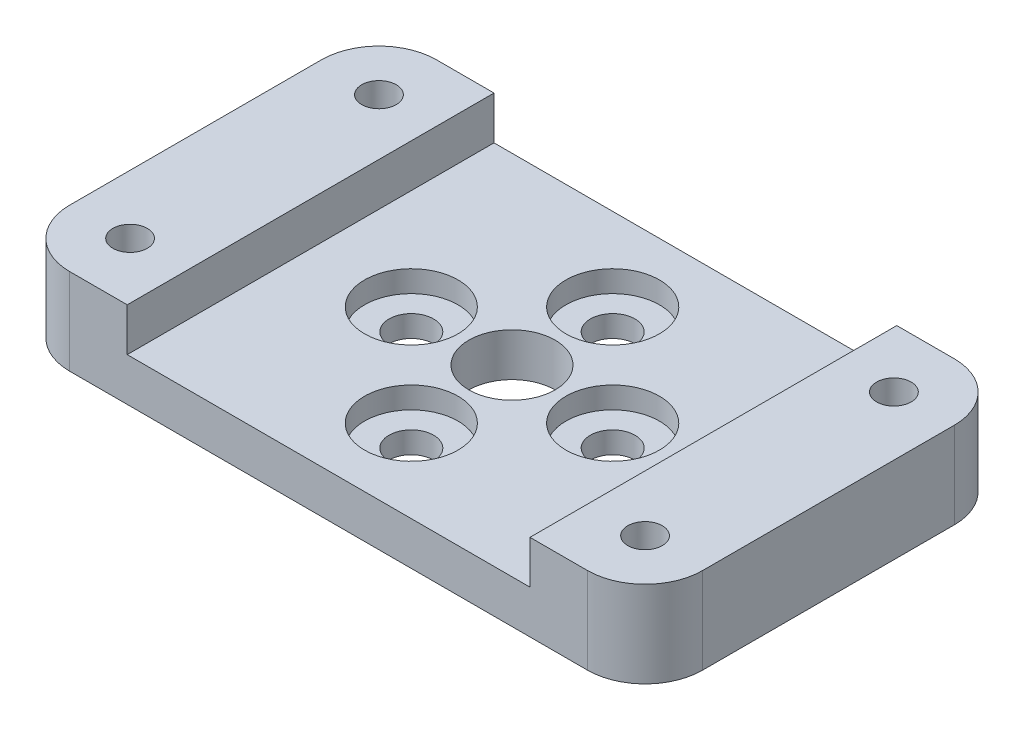
SolidWorks part; units mm, degrees
ref_plane "前视基准面" through (0, 0, 0) normal (0, 0, 1) x (1, 0, 0)
ref_plane "上视基准面" through (0, 0, 0) normal (0, 1, 0) x (1, 0, 0)
ref_plane "右视基准面" through (0, 0, 0) normal (1, 0, 0) x (0, 0, -1)
other "Configuration Table"
sketch "草图1" plane through (0, 0, 0) normal (0, 1, 0) x (1, 0, 0)
  line L0 (-13.2993, 0) -> (13.5934, 0) construction
  line L1 (0, 16.6571) -> (0, -12.7411) construction
  line L3 (22, -12.75) -> (-22, -12.75)
  line L4 (22, -12.75) -> (22, 12.75)
  line L5 (22, 12.75) -> (-22, 12.75)
  line L6 (-22, -12.75) -> (-22, 12.75)
  line L7 (22, -12.75) -> (-22, 12.75) construction
  line L8 (22, 12.75) -> (-22, -12.75) construction
  circle A0 centre (0, 0) radius 7 construction
  circle A1 centre (7, 0) radius 1.55
  circle A2 centre (0, -7) radius 1.55
  circle A3 centre (-7, 0) radius 1.55
  circle A4 centre (0, 7) radius 1.55
  circle A5 centre (-17.9, 8.65) radius 1.2
  circle A6 centre (17.9, 8.65) radius 1.2
  circle A7 centre (-17.9, -8.65) radius 1.2
  circle A8 centre (17.9, -8.65) radius 1.2
  circle A9 centre (0, 0) radius 3
  point P18 (0, 0)
  dimension "D1" = 14
  dimension "D2" = 3.1
  dimension "D4" = 35.8
  dimension "D5" = 17.3
  dimension "D6" = 2.4
  dimension "D7" = 44
  dimension "D8" = 25.5
  dimension "D3" = 4
extrude "凸台-拉伸1" add sketch "草图1" along normal blind 3
sketch "草图3" plane through (0, 0, 0) normal (0, -1, 0) x (1, 0, 0)
  line L0 (0, 16.577) -> (0, -17.2201) construction
  line L1 (22, -12.75) -> (-22, -12.75) construction
  line L2 (-22, 12.75) -> (-14, 12.75)
  line L3 (-22, 12.75) -> (-22, -12.75)
  line L4 (-22, -12.75) -> (-14, -12.75)
  line L5 (-14, 12.75) -> (-14, -12.75)
  line L6 (22, -12.75) -> (14, -12.75)
  line L7 (14, 12.75) -> (14, -12.75)
  line L8 (22, 12.75) -> (14, 12.75)
  line L9 (22, 12.75) -> (22, -12.75)
  circle A0 centre (17.9, -8.65) radius 1.2 construction
  circle A1 centre (17.9, 8.65) radius 1.2 construction
  circle A2 centre (-17.9, -8.65) radius 1.2 construction
  circle A3 centre (-17.9, 8.65) radius 1.2 construction
  circle A4 centre (17.9, -8.65) radius 1.2
  circle A5 centre (17.9, 8.65) radius 1.2
  circle A6 centre (-17.9, -8.65) radius 1.2
  circle A7 centre (-17.9, 8.65) radius 1.2
  dimension "D1" = 8
extrude "凸台-拉伸2" add sketch "草图3" against normal blind 6
fillet "圆角1" radius 4 4 edges at (-22, 3, -12.75) (-22, 3, 12.75) (22, 3, 12.75) (22, 3, -12.75)
sketch "草图2" plane through (0, 3, 0) normal (0, 1, 0) x (1, 0, 0)
  circle A0 centre (7, 0) radius 3.25
  circle A1 centre (0, -7) radius 3.25
  circle A2 centre (-7, 0) radius 3.25
  circle A3 centre (0, 7) radius 3.25
  point P12 (0, 0)
  dimension "D1" = 6.5
  dimension "D2" = 4
extrude "切除-拉伸1" cut sketch "草图2" against normal blind 1.5
chamfer "倒角1" distance 1.5 angle 45 4 edges at (17.9, 0, -9.85) (17.9, 0, 9.85) (-17.9, 0, 7.45) (-17.9, 0, -7.45)
